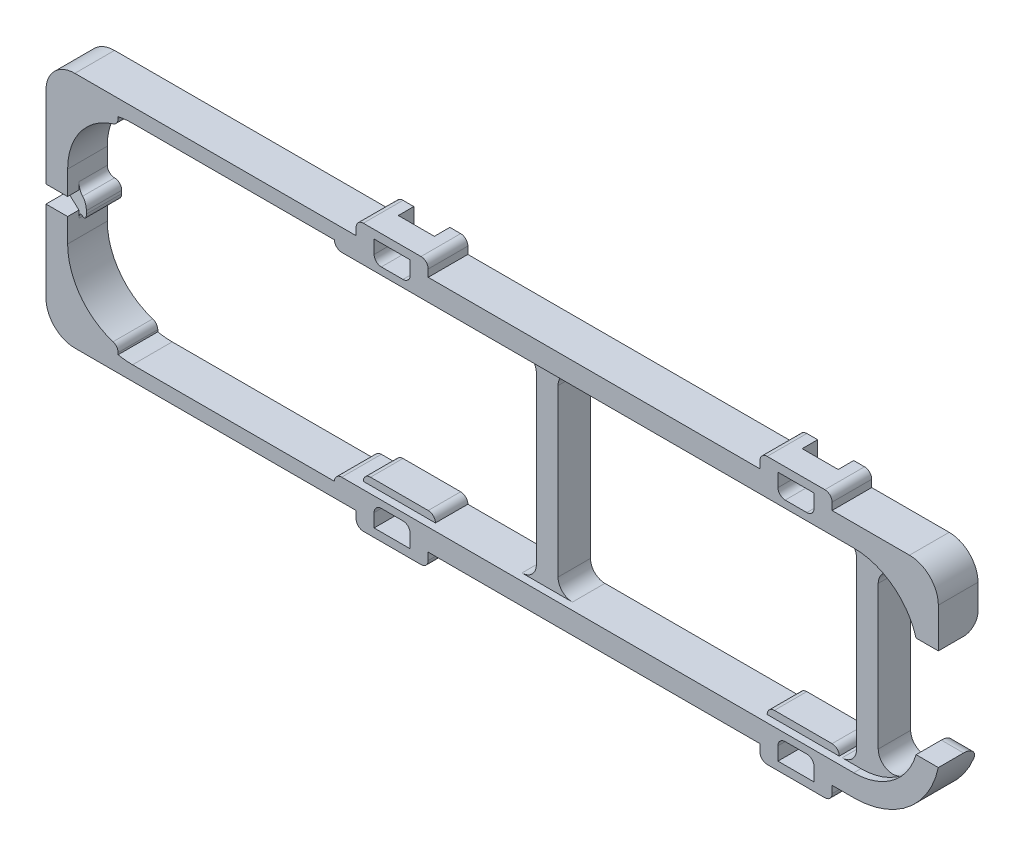
SolidWorks part; units mm, degrees
ref_plane "Front" through (0, 0, 0) normal (0, 0, 1) x (1, 0, 0)
ref_plane "Top" through (0, 0, 0) normal (0, 1, 0) x (1, 0, 0)
ref_plane "Right" through (0, 0, 0) normal (1, 0, 0) x (0, 0, -1)
sketch "Sketch1 - footprint" plane through (0, 0, 0) normal (0, 0, 1) x (1, 0, 0)
  line L1 (10, 14.5) -> (110, 14.5) construction
  line L2 (0, 4.5) -> (0, -4.5) construction
  line L3 (10, -14.5) -> (110, -14.5) construction
  line L4 (120, 4.5) -> (120, -4.5) construction
  arc A0 (110, 14.5) -> (120, 4.5) centre (110, 4.5) cw construction
  arc A1 (120, -4.5) -> (110, -14.5) centre (110, -4.5) cw construction
  arc A2 (10, -14.5) -> (0, -4.5) centre (10, -4.5) cw construction
  arc A3 (0, 4.5) -> (10, 14.5) centre (10, 4.5) cw construction
  point P4 (0, 0)
  point P8 (120, 14.5)
  point P13 (0, -14.5)
  point P16 (0, 14.5)
  dimension "D3" = 10
  dimension "D1" = 120
  dimension "D2" = 29
sketch "Sketch2" plane through (0, 0, 0) normal (0, 0, 1) x (1, 0, 0)
  line L4 (122.25, -4.5) -> (122.25, 4.5)
  line L5 (110, 16.75) -> (10, 16.75)
  line L6 (-2.25, 4.5) -> (-2.25, -4.5)
  line L7 (10, -16.75) -> (110, -16.75)
  line L8 (120.25, -4.5) -> (120.25, 4.5)
  line L9 (10, -14.75) -> (110, -14.75)
  line L10 (-0.25, 4.5) -> (-0.25, -4.5)
  line L11 (110, 14.75) -> (10, 14.75)
  line L12 (120.25, -4.5) -> (120.25, 4.5)
  line L13 (10, -14.75) -> (110, -14.75)
  line L14 (-0.25, 4.5) -> (-0.25, -4.5)
  line L15 (110, 14.75) -> (10, 14.75)
  arc A4 (122.25, 4.5) -> (110, 16.75) centre (110, 4.5) ccw
  arc A5 (10, 16.75) -> (-2.25, 4.5) centre (10, 4.5) ccw
  arc A6 (-2.25, -4.5) -> (10, -16.75) centre (10, -4.5) ccw
  arc A7 (110, -16.75) -> (122.25, -4.5) centre (110, -4.5) ccw
  arc A8 (120.25, 4.5) -> (110, 14.75) centre (110, 4.5) ccw
  arc A9 (110, -14.75) -> (120.25, -4.5) centre (110, -4.5) ccw
  arc A10 (-0.25, -4.5) -> (10, -14.75) centre (10, -4.5) ccw
  arc A11 (10, 14.75) -> (-0.25, 4.5) centre (10, 4.5) ccw
  arc A12 (120.25, 4.5) -> (110, 14.75) centre (110, 4.5) ccw
  arc A13 (110, -14.75) -> (120.25, -4.5) centre (110, -4.5) ccw
  arc A14 (-0.25, -4.5) -> (10, -14.75) centre (10, -4.5) ccw
  arc A15 (10, 14.75) -> (-0.25, 4.5) centre (10, 4.5) ccw
  dimension "D1" = 0.25
  dimension "D2" = 2
ref_plane "Plane1 - PCB bottom plane" through (0, 0, -1.6194) normal (0, 0, 1) x (1, 0, 0)
sketch "Sketch3" plane through (0, 0, -1.6194) normal (0, 0, 1) x (1, 0, 0)
  line L9 (119, -4.5) -> (119, 4.5)
  line L10 (10, -13.5) -> (110, -13.5)
  line L11 (1, 4.5) -> (1, -4.5)
  line L12 (110, 13.5) -> (10, 13.5)
  line L13 (119, -4.5) -> (119, 4.5)
  line L14 (10, -13.5) -> (110, -13.5)
  line L15 (1, 4.5) -> (1, -4.5)
  line L16 (110, 13.5) -> (10, 13.5)
  line L24 (110, 16.5) -> (10, 16.5)
  line L25 (122, -4.5) -> (122, 4.5)
  line L26 (10, -16.5) -> (110, -16.5)
  line L27 (-2, 4.5) -> (-2, -4.5)
  line L28 (110, 16.5) -> (10, 16.5)
  line L29 (122, -4.5) -> (122, 4.5)
  line L30 (10, -16.5) -> (110, -16.5)
  line L31 (-2, 4.5) -> (-2, -4.5)
  arc A8 (119, 4.5) -> (110, 13.5) centre (110, 4.5) ccw
  arc A9 (110, -13.5) -> (119, -4.5) centre (110, -4.5) ccw
  arc A10 (1, -4.5) -> (10, -13.5) centre (10, -4.5) ccw
  arc A11 (10, 13.5) -> (1, 4.5) centre (10, 4.5) ccw
  arc A12 (119, 4.5) -> (110, 13.5) centre (110, 4.5) ccw
  arc A13 (110, -13.5) -> (119, -4.5) centre (110, -4.5) ccw
  arc A14 (1, -4.5) -> (10, -13.5) centre (10, -4.5) ccw
  arc A15 (10, 13.5) -> (1, 4.5) centre (10, 4.5) ccw
  arc A23 (122, 4.5) -> (110, 16.5) centre (110, 4.5) ccw
  arc A24 (110, -16.5) -> (122, -4.5) centre (110, -4.5) ccw
  arc A25 (-2, -4.5) -> (10, -16.5) centre (10, -4.5) ccw
  arc A26 (10, 16.5) -> (-2, 4.5) centre (10, 4.5) ccw
  arc A27 (122, 4.5) -> (110, 16.5) centre (110, 4.5) ccw
  arc A28 (110, -16.5) -> (122, -4.5) centre (110, -4.5) ccw
  arc A29 (-2, -4.5) -> (10, -16.5) centre (10, -4.5) ccw
  arc A30 (10, 16.5) -> (-2, 4.5) centre (10, 4.5) ccw
  dimension "D1" = 1
  dimension "D2" = 2
extrude "Boss-Extrude2" add sketch "Sketch3" against normal blind 5.5
sketch "Sketch4" plane through (0, 0, -1.6194) normal (0, 0, 1) x (1, 0, 0)
  line L6 (88, -13.5) -> (88, 13.5) construction
  line L7 (10, -13.5) -> (110, -13.5) construction
  line L9 (110, 13.5) -> (10, 13.5) construction
  line L10 (120, 4.5) -> (120, -4.5) construction
  line L11 (10, -13.5) -> (110, -13.5) construction
  line L12 (109.4, -13.5) -> (112.4, -13.5)
  line L13 (109.4, -13.5) -> (109.4, 13.5)
  line L14 (109.4, 13.5) -> (112.4, 13.5)
  line L15 (112.4, -13.5) -> (112.4, 13.5)
  line L17 (65, -13.5) -> (68, -13.5)
  line L18 (65, -13.5) -> (65, 13.5)
  line L19 (65, 13.5) -> (68, 13.5)
  line L20 (68, -13.5) -> (68, 13.5)
  point P16 (120, 0)
  dimension "D1" = 32
  dimension "D2" = 3
  dimension "D3" = 7.6
  dimension "D4" = 3
  dimension "D5" = 52
  dimension "D6" = 20
extrude "Boss-Extrude4 - cross structures" add sketch "Sketch4" against normal up to surface (5.5 mm away) up to face at (60, 0, -7.1194)
sketch "Sketch6" plane through (0, 0, -1.6194) normal (0, 0, 1) x (1, 0, 0)
  line L0 (109.4, 13.5) -> (110, 13.5)
  line L1 (112.4, 13.1741) -> (112.4, -13.1741)
  line L2 (109.4, -13.5) -> (110, -13.5)
  line L4 (109.4, -13.5) -> (112.4, -13.5)
  line L5 (112.4, -13.5) -> (112.4, 13.5)
  line L6 (112.4, 13.5) -> (109.4, 13.5)
  line L7 (109.4, 13.5) -> (109.4, -13.5)
  line L11 (109.4, 13.5) -> (109.4, -13.5)
  line L12 (65, -13.5) -> (68, -13.5)
  line L13 (68, -13.5) -> (68, 13.5)
  line L14 (68, 13.5) -> (65, 13.5)
  line L15 (65, 13.5) -> (65, -13.5)
  line L16 (65, -13.5) -> (68, -13.5)
  line L17 (68, -13.5) -> (68, 13.5)
  line L18 (68, 13.5) -> (65, 13.5)
  line L19 (65, 13.5) -> (65, -13.5)
  arc A0 (110, 13.5) -> (112.4, 13.1741) centre (110, 4.5) cw
  arc A1 (119, 4.5) -> (112.4, 13.1741) centre (110, 4.5) ccw construction
  arc A2 (110, -13.5) -> (112.4, -13.1741) centre (110, -4.5) ccw
  arc A3 (112.4, -13.1741) -> (119, -4.5) centre (110, -4.5) ccw construction
  dimension "D1" = 0
  dimension "D2" = 0
extrude "Cut-Extrude3 - 1 mm spacing" cut sketch "Sketch6" against normal blind 1
sketch "Sketch7" plane through (0, 0, -1.6194) normal (0, 0, 1) x (1, 0, 0)
  line L0 (10, -14.5) -> (110, -14.5) construction
  line L1 (38, -14.5) -> (10, -14.5)
  line L2 (38, -14.5) -> (38, 14.5)
  line L3 (38, 14.5) -> (10, 14.5)
  line L5 (10, 14.5) -> (110, 14.5) construction
  line L6 (0, 4.5) -> (0, -4.5) construction
  line L7 (8, 14.298) -> (8, -14.298)
  arc A0 (10, 14.5) -> (0, 4.5) centre (10, 4.5) ccw construction
  arc A1 (0, -4.5) -> (10, -14.5) centre (10, -4.5) ccw construction
  arc A2 (10, -14.5) -> (8, -14.298) centre (10, -4.5) cw
  arc A3 (10, 14.5) -> (8, 14.298) centre (10, 4.5) ccw
  dimension "D1" = 38
  dimension "D2" = 30
extrude "Cut-Extrude4 - electronics spacing" cut sketch "Sketch7" against normal through all
sketch "Sketch8" plane through (122, 0, 0) normal (1, 0, 0) x (0, 0, -1)
  line L0 (1.6194, -7) -> (7.1194, -7)
  line L1 (1.6194, -4.5) -> (1.6194, -16.5) construction
  line L2 (7.1194, -7) -> (7.1194, 7)
  line L3 (7.1194, 7) -> (1.6194, 7)
  line L4 (1.6194, 16.5) -> (1.6194, 4.5) construction
  line L5 (1.6194, -7) -> (1.6194, 7)
  line L6 (7.1194, -4.5) -> (7.1194, 4.5) construction
  point P8 (1.6194, 0)
  dimension "D1" = 14
extrude "Cut-Extrude2 - USB-C cutout" cut sketch "Sketch8" against normal blind 5
sketch "Sketch10" plane through (0, 0, -1.6194) normal (0, 0, 1) x (1, 0, 0)
  line L1 (1, 1.2) -> (3, 1.2)
  line L2 (1, 1.2) -> (1, -1.2)
  line L3 (1, -1.2) -> (3, -1.2)
  line L4 (3, 1.2) -> (3, -1.2)
  line L5 (1, 4.5) -> (1, -4.5) construction
  point P6 (1, 0)
  dimension "D1" = 2.4
  dimension "D2" = 2
extrude "Boss-Extrude3" add sketch "Sketch10" against normal up to surface (5.5 mm away) contours L4 L3 L2 L1 up to face at (23.7799, 0, -7.1194)
sketch "Sketch11" plane through (0, 0, 0) normal (0, 1, 0) x (1, 0, 0)
  line L0 (3, 2.2194) -> (-2, 4.6194)
  line L1 (3, 7.1194) -> (3, 1.6194) construction
  line L2 (-2, 7.1194) -> (-2, 1.6194) construction
  line L3 (-2, 4.6194) -> (-2, 1.6194)
  line L4 (-2, 1.6194) -> (3, 1.6194)
  line L5 (3, 1.6194) -> (3, 2.2194)
  dimension "D1" = 0.6
  dimension "D2" = 3
extrude "Cut-Extrude1 - LED opening" cut sketch "Sketch11" against normal mid plane 2.4
sketch "Sketch12" plane through (0, 0, -7.1194) normal (0, 0, -1) x (-1, 0, 0)
  line L0 (-10, -16.5) -> (-110, -16.5) construction
  line L1 (-41, -16.5) -> (-51, -16.5)
  line L2 (-41, -16.5) -> (-41, -18.5)
  line L3 (-41, -18.5) -> (-51, -18.5)
  line L4 (-51, -16.5) -> (-51, -18.5)
  line L6 (-97, -16.5) -> (-107, -16.5)
  line L7 (-97, -16.5) -> (-97, -18.5)
  line L8 (-97, -18.5) -> (-107, -18.5)
  line L9 (-107, -16.5) -> (-107, -18.5)
  point P10 (-46, -16.5)
  point P12 (-102, -16.5)
  dimension "D1" = 46
  dimension "D2" = 102
  dimension "D3" = 10
  dimension "D4" = 2
extrude "Boss-Extrude4 - snap bumps" add sketch "Sketch12" against normal up to surface (5.5 mm away) up to face at (40.6517, -10.6611, -1.6194)
sketch "Sketch13" plane through (0, 0, -7.1194) normal (0, 0, -1) x (-1, 0, 0)
  line L0 (-51, -18.5) -> (-41, -18.5) construction
  line L1 (-43.5, -18.5) -> (-48.5, -18.5)
  line L2 (-43.5, -18.5) -> (-43.5, -14.5)
  line L3 (-43.5, -14.5) -> (-48.5, -14.5)
  line L4 (-48.5, -18.5) -> (-48.5, -14.5)
  line L6 (-107, -18.5) -> (-97, -18.5) construction
  line L7 (-99.5, -18.5) -> (-104.5, -18.5)
  line L8 (-99.5, -18.5) -> (-99.5, -14.5)
  line L9 (-99.5, -14.5) -> (-104.5, -14.5)
  line L10 (-104.5, -18.5) -> (-104.5, -14.5)
  point P8 (-46, -18.5)
  point P9 (-46, -18.5)
  point P14 (-102, -18.5)
  point P15 (-102, -18.5)
  dimension "D1" = 5
  dimension "D2" = 4
extrude "Cut-Extrude2 - snap seat (2.15, original is 2.0)" cut sketch "Sketch13" against normal blind 2.15
sketch "Sketch14" plane through (0, 0, -4.9694) normal (0, 0, -1) x (-1, 0, 0)
  line L0 (-48.5, -14.5) -> (-48.5, -18.5) construction
  line L1 (-43.5, -14.5) -> (-48.5, -14.5)
  line L2 (-43.5, -14.5) -> (-43.5, -17.35)
  line L3 (-43.5, -17.35) -> (-48.5, -17.35)
  line L4 (-48.5, -14.5) -> (-48.5, -17.35)
  line L6 (-51, -16.5) -> (-97, -16.5) construction
  line L7 (-99.5, -14.5) -> (-104.5, -14.5)
  line L8 (-99.5, -14.5) -> (-99.5, -17.35)
  line L9 (-99.5, -17.35) -> (-104.5, -17.35)
  line L10 (-104.5, -14.5) -> (-104.5, -17.35)
  line L13 (-99.5, -18.5) -> (-99.5, -14.5) construction
  dimension "D1" = 0.85
extrude "Cut-Extrude3 - snap post cut" cut sketch "Sketch14" against normal through all
sketch "Sketch15" plane through (0, 0, -7.1194) normal (0, 0, -1) x (-1, 0, 0)
  line L0 (-38, -13.5) -> (-65, -13.5) construction
  line L1 (-41, -13.5) -> (-51, -13.5)
  line L2 (-41, -13.5) -> (-41, -12.5)
  line L3 (-41, -12.5) -> (-51, -12.5)
  line L4 (-51, -13.5) -> (-51, -12.5)
  line L5 (-68, -13.5) -> (-109.4, -13.5) construction
  line L6 (-97, -13.5) -> (-107, -13.5)
  line L7 (-97, -13.5) -> (-97, -12.5)
  line L8 (-97, -12.5) -> (-107, -12.5)
  line L9 (-107, -13.5) -> (-107, -12.5)
  line L10 (-41, -18.5) -> (-41, -16.5) construction
  line L11 (-51, -16.5) -> (-51, -18.5) construction
  line L12 (-97, -18.5) -> (-97, -16.5) construction
  line L13 (-107, -16.5) -> (-107, -18.5) construction
  dimension "D1" = 1
extrude "Boss-Extrude4" add sketch "Sketch15" against normal up to surface (4.5 mm away) up to face at (66.5, 0, -2.6194)
mirror "Mirror1" about plane through (0, 0, 0) normal (0, 1, 0) of "Cut-Extrude2 - snap seat (2.15, original is 2.0)", "Boss-Extrude4 - snap bumps", "Cut-Extrude3 - snap post cut", "Boss-Extrude4"
fillet "Fillet2 - USBC port" [suppressed] radius 2
fillet "Fillet3" radius 1 4 edges at (38, 13.5, -4.3694) (38, -13.5, -4.3694) (8, -13.275, -4.3694) (8, 13.275, -4.3694)
fillet "Fillet4" radius 1 4 edges at (1, 1.2, -5.1494) (3, 1.2, -4.6694) (3, -1.2, -4.6694) (1, -1.2, -5.1494)
fillet "Fillet5" radius 2 8 edges at (112.4, -13.1741, -4.8694) (112.4, 13.1741, -4.8694) (109.4, 13.5, -4.8694) (109.4, -13.5, -4.8694) (68, -13.5, -4.8694) (68, 13.5, -4.8694) (65, 13.5, -4.8694) (65, -13.5, -4.8694)
fillet "Fillet6 - snap features" radius 1 24 edges at (48.5, -14.5, -4.3694) (43.5, -14.5, -4.3694) (51, -18.5, -4.3694) (51, -12.5, -4.8694) (41, -12.5, -4.8694) (41, -18.5, -4.3694) (41, 12.5, -4.8694) (51, 12.5, -4.8694) (43.5, 14.5, -4.3694) (51, 18.5, -4.3694) (48.5, 14.5, -4.3694) (41, 18.5, -4.3694) (104.5, 14.5, -4.3694) (99.5, 14.5, -4.3694) (107, 18.5, -4.3694) (107, 12.5, -4.8694) (97, 12.5, -4.8694) (97, 18.5, -4.3694) (104.5, -14.5, -4.3694) (99.5, -14.5, -4.3694) (107, -18.5, -4.3694) (107, -12.5, -4.8694) (97, -12.5, -4.8694) (97, -18.5, -4.3694)
sketch "Sketch16" plane through (0, 0, -7.1194) normal (0, 0, -1) x (-1, 0, 0)
  line L0 (-98, -12.5) -> (-106, -12.5) construction
  line L1 (-109.4, -11.5) -> (-109.4, 11.5) construction
  line L2 (-98, 12.5) -> (-106, 12.5) construction
  line L3 (-97, 13.5) -> (-70, 13.5) construction
  line L4 (-70, -13.5) -> (-97, -13.5) construction
  line L5 (-68, 11.5) -> (-68, -11.5) construction
  line L6 (-38, 14.5) -> (-10, 14.5) construction
  line L7 (-41, 13.5) -> (-39, 13.5) construction
  line L8 (-42, 12.5) -> (-50, 12.5) construction
  line L9 (-63, 13.5) -> (-51, 13.5) construction
  line L10 (-65, -11.5) -> (-65, 11.5) construction
  line L11 (-51, -13.5) -> (-63, -13.5) construction
  line L12 (-42, -12.5) -> (-50, -12.5) construction
  line L13 (-39, -13.5) -> (-41, -13.5) construction
  line L14 (-10, -14.5) -> (-38, -14.5) construction
  line L15 (-98, -12.5) -> (-106, -12.5)
  line L16 (-109.4, -11.5) -> (-109.4, 11.5)
  line L17 (-98, 12.5) -> (-106, 12.5)
  line L18 (-97, 13.5) -> (-70, 13.5)
  line L19 (-70, -13.5) -> (-97, -13.5)
  line L20 (-68, 11.5) -> (-68, -11.5)
  line L21 (-38, 14.5) -> (-10, 14.5)
  line L22 (-41, 13.5) -> (-39, 13.5)
  line L23 (-42, 12.5) -> (-50, 12.5)
  line L24 (-63, 13.5) -> (-51, 13.5)
  line L25 (-65, -11.5) -> (-65, 11.5)
  line L26 (-51, -13.5) -> (-63, -13.5)
  line L27 (-42, -12.5) -> (-50, -12.5)
  line L28 (-39, -13.5) -> (-41, -13.5)
  line L29 (-10, -14.5) -> (-38, -14.5)
  line L30 (-1, -2.2) -> (-1, -4.5) construction
  line L31 (-1, -2.2) -> (-1, -4.5)
  line L32 (-1, 4.5) -> (-1, 2.2) construction
  line L33 (-1, 4.5) -> (-1, 2.2)
  line L34 (-107, -13.5) -> (-107.4, -13.5) construction
  line L35 (-107, -13.5) -> (-107.4, -13.5)
  line L36 (-107.4, 13.5) -> (-107, 13.5) construction
  line L37 (-107.4, 13.5) -> (-107, 13.5)
  line L38 (-3, -0.2) -> (-3, 0.2) construction
  line L39 (-3, -0.2) -> (-3, 0.2)
  line L40 (-8, -14.0394) -> (-8, -14.298) construction
  line L41 (-8, -14.0394) -> (-8, -14.298)
  line L42 (-8, 14.298) -> (-8, 14.0394) construction
  line L43 (-8, 14.298) -> (-8, 14.0394)
  arc A0 (-97, -13.5) -> (-98, -12.5) centre (-98, -13.5) ccw construction
  arc A1 (-106, -12.5) -> (-107, -13.5) centre (-106, -13.5) ccw construction
  arc A2 (-109.4, -11.5) -> (-107.4, -13.5) centre (-107.4, -11.5) ccw construction
  arc A3 (-107.4, 13.5) -> (-109.4, 11.5) centre (-107.4, 11.5) ccw construction
  arc A4 (-107, 13.5) -> (-106, 12.5) centre (-106, 13.5) ccw construction
  arc A5 (-98, 12.5) -> (-97, 13.5) centre (-98, 13.5) ccw construction
  arc A6 (-70, -13.5) -> (-68, -11.5) centre (-70, -11.5) ccw construction
  arc A7 (-68, 11.5) -> (-70, 13.5) centre (-70, 11.5) ccw construction
  arc A8 (-1, -2.2) -> (-2, -1.2) centre (-2, -2.2) ccw construction
  arc A9 (-3, -0.2) -> (-2, -1.2) centre (-2, -0.2) ccw construction
  arc A10 (-2, 1.2) -> (-3, 0.2) centre (-2, 0.2) ccw construction
  arc A11 (-2, 1.2) -> (-1, 2.2) centre (-2, 2.2) ccw construction
  arc A12 (-1, 4.5) -> (-7.3, 13.0855) centre (-10, 4.5) ccw construction
  arc A13 (-8, 14.0394) -> (-7.3, 13.0855) centre (-7, 14.0394) ccw construction
  arc A14 (-8, 14.298) -> (-10, 14.5) centre (-10, 4.5) ccw construction
  arc A15 (-39, 13.5) -> (-38, 14.5) centre (-39, 14.5) ccw construction
  arc A16 (-42, 12.5) -> (-41, 13.5) centre (-42, 13.5) ccw construction
  arc A17 (-51, 13.5) -> (-50, 12.5) centre (-50, 13.5) ccw construction
  arc A18 (-63, 13.5) -> (-65, 11.5) centre (-63, 11.5) ccw construction
  arc A19 (-65, -11.5) -> (-63, -13.5) centre (-63, -11.5) ccw construction
  arc A20 (-50, -12.5) -> (-51, -13.5) centre (-50, -13.5) ccw construction
  arc A21 (-41, -13.5) -> (-42, -12.5) centre (-42, -13.5) ccw construction
  arc A22 (-38, -14.5) -> (-39, -13.5) centre (-39, -14.5) ccw construction
  arc A23 (-10, -14.5) -> (-8, -14.298) centre (-10, -4.5) ccw construction
  arc A24 (-7.3, -13.0855) -> (-8, -14.0394) centre (-7, -14.0394) ccw construction
  arc A25 (-7.3, -13.0855) -> (-1, -4.5) centre (-10, -4.5) ccw construction
  arc A26 (-97, -13.5) -> (-98, -12.5) centre (-98, -13.5) ccw
  arc A27 (-106, -12.5) -> (-107, -13.5) centre (-106, -13.5) ccw
  arc A28 (-109.4, -11.5) -> (-107.4, -13.5) centre (-107.4, -11.5) ccw
  arc A29 (-107.4, 13.5) -> (-109.4, 11.5) centre (-107.4, 11.5) ccw
  arc A30 (-107, 13.5) -> (-106, 12.5) centre (-106, 13.5) ccw
  arc A31 (-98, 12.5) -> (-97, 13.5) centre (-98, 13.5) ccw
  arc A32 (-70, -13.5) -> (-68, -11.5) centre (-70, -11.5) ccw
  arc A33 (-68, 11.5) -> (-70, 13.5) centre (-70, 11.5) ccw
  arc A34 (-1, -2.2) -> (-2, -1.2) centre (-2, -2.2) ccw
  arc A35 (-3, -0.2) -> (-2, -1.2) centre (-2, -0.2) ccw
  arc A36 (-2, 1.2) -> (-3, 0.2) centre (-2, 0.2) ccw
  arc A37 (-2, 1.2) -> (-1, 2.2) centre (-2, 2.2) ccw
  arc A38 (-1, 4.5) -> (-7.3, 13.0855) centre (-10, 4.5) ccw
  arc A39 (-8, 14.0394) -> (-7.3, 13.0855) centre (-7, 14.0394) ccw
  arc A40 (-8, 14.298) -> (-10, 14.5) centre (-10, 4.5) ccw
  arc A41 (-39, 13.5) -> (-38, 14.5) centre (-39, 14.5) ccw
  arc A42 (-42, 12.5) -> (-41, 13.5) centre (-42, 13.5) ccw
  arc A43 (-51, 13.5) -> (-50, 12.5) centre (-50, 13.5) ccw
  arc A44 (-63, 13.5) -> (-65, 11.5) centre (-63, 11.5) ccw
  arc A45 (-65, -11.5) -> (-63, -13.5) centre (-63, -11.5) ccw
  arc A46 (-50, -12.5) -> (-51, -13.5) centre (-50, -13.5) ccw
  arc A47 (-41, -13.5) -> (-42, -12.5) centre (-42, -13.5) ccw
  arc A48 (-38, -14.5) -> (-39, -13.5) centre (-39, -14.5) ccw
  arc A49 (-10, -14.5) -> (-8, -14.298) centre (-10, -4.5) ccw
  arc A50 (-7.3, -13.0855) -> (-8, -14.0394) centre (-7, -14.0394) ccw
  arc A51 (-7.3, -13.0855) -> (-1, -4.5) centre (-10, -4.5) ccw
extrude "Boss-Extrude5" [suppressed] add sketch "Sketch16" against normal blind 1
sketch "Sketch17" [suppressed] plane through (0, 0, -7.1194) normal (0, 0, -1) x (-1, 0, 0)
  line L0 (-112.4, 9.9443) -> (-112.4, -9.9443) construction
  line L1 (-112.4, 9.9443) -> (-112.4, -9.9443)
  arc A0 (-117.7942, -9) -> (-115.6571, -11.4998) centre (-110, -4.5) ccw construction
  arc A1 (-115.6571, -11.4998) -> (-112.4, -9.9443) centre (-114.4, -9.9443) ccw construction
  arc A2 (-112.4, 9.9443) -> (-115.6571, 11.4998) centre (-114.4, 9.9443) ccw construction
  arc A3 (-115.6571, 11.4998) -> (-117.7942, 9) centre (-110, 4.5) ccw construction
  arc A4 (-117.7942, -9) -> (-115.6571, -11.4998) centre (-110, -4.5) ccw
  arc A5 (-115.6571, -11.4998) -> (-112.4, -9.9443) centre (-114.4, -9.9443) ccw
  arc A6 (-112.4, 9.9443) -> (-115.6571, 11.4998) centre (-114.4, 9.9443) ccw
  arc A7 (-115.6571, 11.4998) -> (-117.7942, 9) centre (-110, 4.5) ccw
  arc A8 (-118.6458, -7) -> (-117.7942, -9) centre (-110, -4.5) ccw construction
  arc A9 (-117.7942, 9) -> (-118.6458, 7) centre (-110, 4.5) ccw construction
  arc A10 (-118.6458, -7) -> (-117.7942, -9) centre (-110, -4.5) ccw
  arc A11 (-117.7942, 9) -> (-118.6458, 7) centre (-110, 4.5) ccw
  arc A12 (-118.6458, 7) -> (-118.6458, -7) centre (-94.4375, 0) ccw
extrude "Boss-Extrude6" [suppressed] add sketch "Sketch17" against normal blind 1
sketch "Sketch18" plane through (0, 0, -1.6194) normal (0, 0, 1) x (1, 0, 0)
  line L0 (110, 16.5) -> (121.7367, 16.5)
  line L1 (121.7367, 16.5) -> (121.7367, 7)
  line L2 (-2, 4.5) -> (-2, 16.5)
  line L3 (-2, 16.5) -> (10, 16.5)
  line L4 (-2, -4.5) -> (-2, -16.5)
  line L5 (-2, -16.5) -> (10, -16.5)
  arc A0 (121.7367, 7) -> (110, 16.5) centre (110, 4.5) ccw construction
  arc A1 (121.7367, 7) -> (110, 16.5) centre (110, 4.5) ccw
  arc A2 (10, 16.5) -> (-2, 4.5) centre (10, 4.5) ccw construction
  arc A3 (10, 16.5) -> (-2, 4.5) centre (10, 4.5) ccw
  arc A4 (-2, -4.5) -> (10, -16.5) centre (10, -4.5) ccw construction
  arc A5 (-2, -4.5) -> (10, -16.5) centre (10, -4.5) ccw
extrude "Boss-Extrude7" add sketch "Sketch18" against normal up to surface (5.5 mm away) up to face at (26.7658, 0, -7.1194)
fillet "Fillet7" radius 4 3 edges at (121.7367, 16.5, -4.3694) (-2, 16.5, -4.3694) (-2, -16.5, -4.3694)
fillet "Fillet8" radius 2 2 edges at (120.1913, 7, -7.1194) (120.1913, -7, -7.1194)
